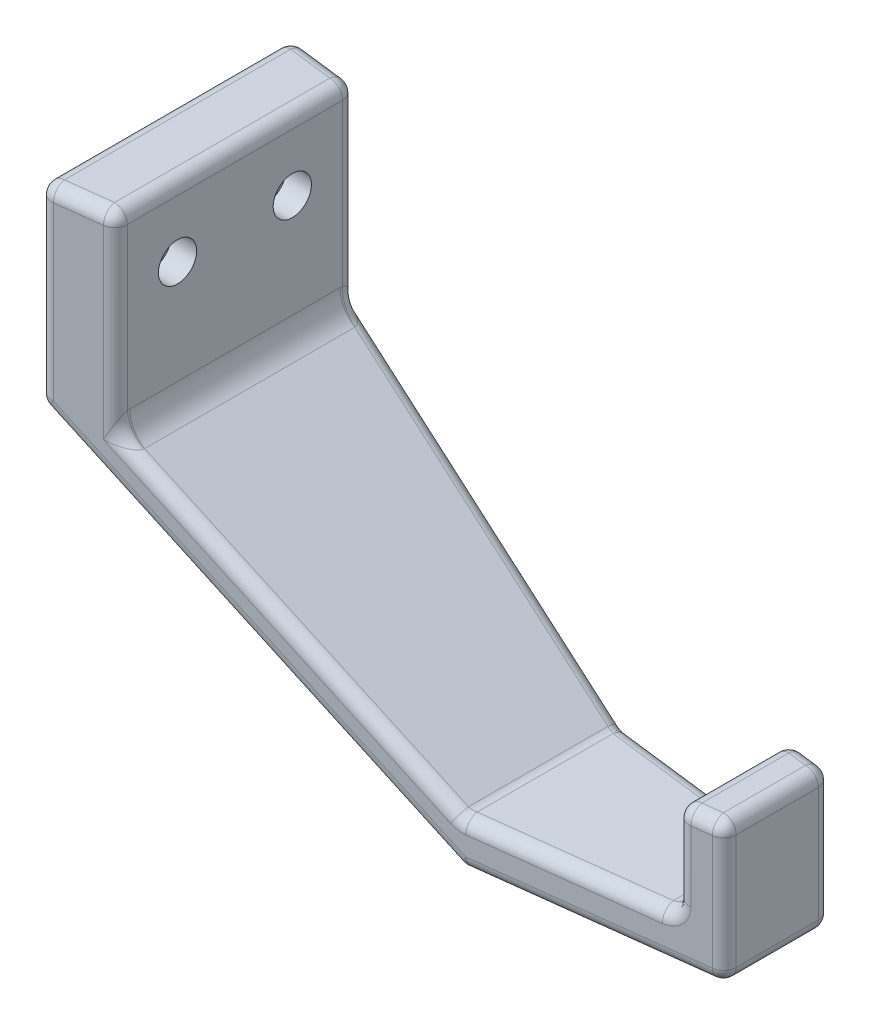
SolidWorks part; units mm, degrees
ref_plane "正面" through (0, 0, 0) normal (0, 0, 1) x (1, 0, 0)
ref_plane "平面" through (0, 0, 0) normal (0, 1, 0) x (1, 0, 0)
ref_plane "右側面" through (0, 0, 0) normal (1, 0, 0) x (0, 0, -1)
sketch "ｽｹｯﾁ1" plane through (0, 0, 0) normal (0, 0, 1) x (1, 0, 0)
  line L0 (0, 0) -> (0, -30)
  line L1 (0, -30) -> (59.0563, -67.5813)
  line L2 (59.0563, -67.5813) -> (96.0563, -67.5813)
  line L3 (96.0563, -67.5813) -> (96.0563, -45.5813)
  line L4 (96.0563, -45.5813) -> (89.0563, -45.5813)
  line L5 (89.0563, -45.5813) -> (89.0563, -60.5813)
  line L6 (89.0563, -60.5813) -> (59.0563, -60.5813)
  line L7 (59.0563, -60.5813) -> (11, -30)
  line L8 (11, -30) -> (11, 0)
  line L9 (11, 0) -> (0, 0)
  dimension "D1" = 30
  dimension "D2" = 30
  dimension "D3" = 11
  dimension "D4" = 37
  dimension "D5" = 7
  dimension "D6" = 30
  dimension "D7" = 15
  dimension "D8" = 22
  dimension "D9" = 70
extrude "ﾎﾞｽ - 押し出し1" add sketch "ｽｹｯﾁ1" along normal blind 40
draft "抜き勾配2" type of draft neutral plane draft angle 7 faces to draft 2 face at (51.0338, -40.7488, 0) face at (51.0338, -40.7488, 40) neutral plane through (0, 0, 40) neutral plane normal (-1, 0, 0) reverse direction yes parameters "D1"=7
sketch "ｽｹｯﾁ2" plane through (0, 0, 0) normal (-1, 0, 0) x (0, 0, 1)
  line L0 (0, 0) -> (0, -30) construction
  line L1 (40, 0) -> (0, 0) construction
  circle A0 centre (11, -11) radius 1.6
  circle A1 centre (29, -11) radius 1.6
  dimension "D1" = 18
  dimension "D2" = 11
  dimension "D3" = 11
  dimension "D4" = 3.2
  dimension "D6" = 3.2
  dimension "D5" = 11
fillet "ﾌｨﾚｯﾄ1" radius 2 29 edges at (96.0563, -67.5813, 20) (89.0563, -60.5813, 20) (96.0563, -56.5813, 11.7942) (96.0563, -56.5813, 28.2058) (89.0563, -53.0813, 10.9347) (89.0563, -53.0813, 29.0653) (96.0563, -45.5813, 20) (92.5563, -45.5813, 11.3645) (89.0563, -45.5813, 20) (92.5563, -45.5813, 28.6355) (77.5563, -67.5813, 30.4773) (77.5563, -67.5813, 9.5227) (74.0563, -60.5813, 9.093) (74.0563, -60.5813, 30.907) (29.5282, -48.7906, 3.6256) (35.0282, -45.2906, 4.3009) (29.5282, -48.7906, 36.3744) (35.0282, -45.2906, 35.6991) (59.0563, -67.5813, 20) (0, -30, 20) (59.0563, -60.5813, 20) (11, -15, 1.3506) (11, -15, 38.6494) (0, -15, 40) (0, -15, 0) (5.5, 0, 39.3247) (5.5, 0, 0.6753) (11, 0, 20) (0, 0, 20)
sketch "ｽｹｯﾁ3" plane through (11, 0, 0) normal (1, 0, 0) x (0, 0, -1)
  circle A0 centre (-11, -11) radius 3
  circle A1 centre (-29, -11) radius 3
  dimension "D1" = 6
  dimension "D2" = 6
  dimension "D4" = 0
  dimension "D3" = 0
  dimension "D5" = 0
extrude "ｶｯﾄ - 押し出し3" cut sketch "ｽｹｯﾁ3" against normal blind 4
extrude "ｶｯﾄ - 押し出し4" cut sketch "ｽｹｯﾁ2" against normal blind 7
fillet "ﾌｨﾚｯﾄ2" radius 5 5 edges at (10.4979, -30.3675, 38.2052) (11, -30.001, 36.8231) (10.4979, -30.3675, 1.7948) (11, -30.001, 3.1769) (11, -30, 20)
